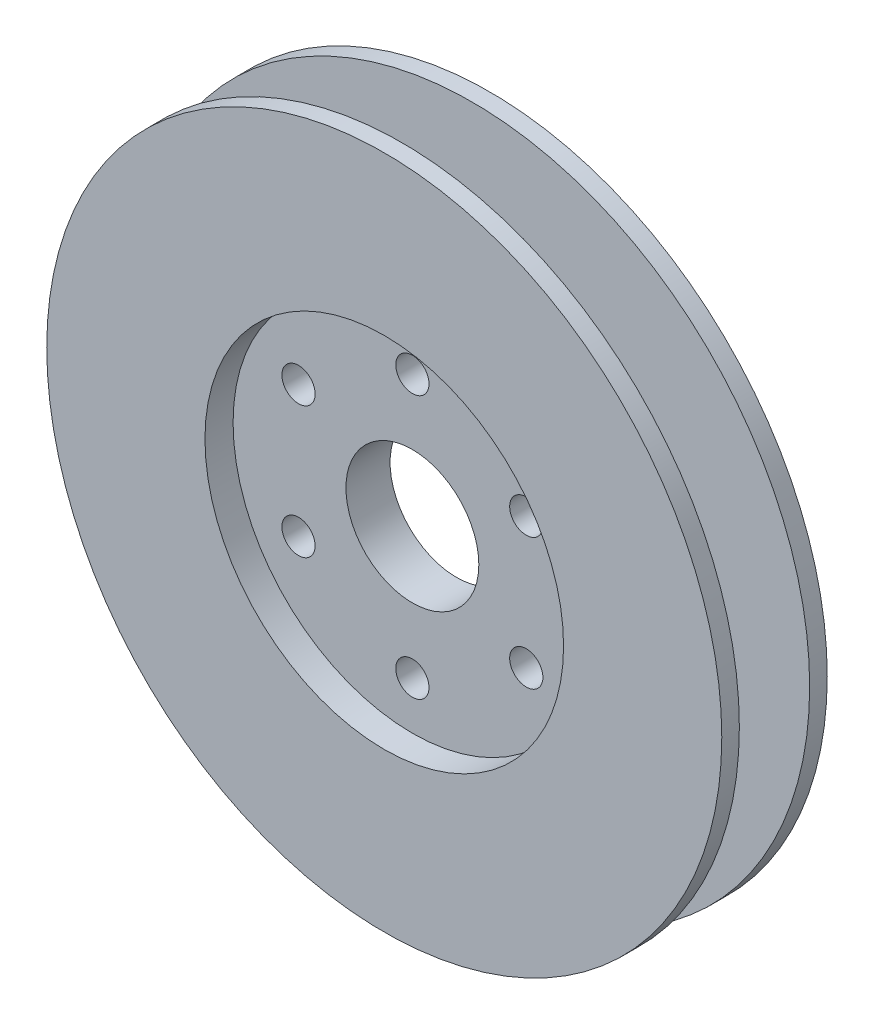
SolidWorks part; units mm, degrees
material "PE High Density Film"
ref_plane "Front Plane" through (0, 0, 0) normal (0, 0, 1) x (1, 0, 0)
ref_plane "Top Plane" through (0, 0, 0) normal (0, 1, 0) x (1, 0, 0)
ref_plane "Right Plane" through (0, 0, 0) normal (1, 0, 0) x (0, 0, -1)
sketch "Sketch1" plane through (0, 0, 0) normal (0, 0, 1) x (1, 0, 0)
  line L0 (0, 0) -> (0, 60.96)
  line L1 (-8.9803, 60.2949) -> (0, 51.3147)
  line L2 (0, 51.3147) -> (8.9803, 60.2949)
  line L3 (36.2849, 48.9849) -> (36.2849, 36.2849)
  line L4 (36.2849, 36.2849) -> (48.9849, 36.2849)
  line L5 (60.2949, 8.9803) -> (51.3147, 0)
  line L6 (51.3147, 0) -> (60.2949, -8.9803)
  line L7 (48.9849, -36.2849) -> (36.2849, -36.2849)
  line L8 (36.2849, -36.2849) -> (36.2849, -48.9849)
  line L9 (8.9803, -60.2949) -> (0, -51.3147)
  line L10 (0, -51.3147) -> (-8.9803, -60.2949)
  line L11 (-36.2849, -48.9849) -> (-36.2849, -36.2849)
  line L12 (-36.2849, -36.2849) -> (-48.9849, -36.2849)
  line L13 (-60.2949, -8.9803) -> (-51.3147, 0)
  line L14 (-51.3147, 0) -> (-60.2949, 8.9803)
  line L15 (-48.9849, 36.2849) -> (-36.2849, 36.2849)
  line L16 (-36.2849, 36.2849) -> (-36.2849, 48.9849)
  arc A0 (-60.2949, -8.9803) -> (-48.9849, -36.2849) centre (0, 0) ccw
  arc A1 (-48.9849, 36.2849) -> (-60.2949, 8.9803) centre (0, 0) ccw
  arc A2 (-36.2849, -48.9849) -> (-8.9803, -60.2949) centre (0, 0) ccw
  arc A3 (8.9803, -60.2949) -> (36.2849, -48.9849) centre (0, 0) ccw
  arc A4 (48.9849, -36.2849) -> (60.2949, -8.9803) centre (0, 0) ccw
  arc A5 (60.2949, 8.9803) -> (48.9849, 36.2849) centre (0, 0) ccw
  arc A6 (36.2849, 48.9849) -> (8.9803, 60.2949) centre (0, 0) ccw
  arc A7 (-8.9803, 60.2949) -> (-36.2849, 48.9849) centre (0, 0) ccw
  circle A8 centre (0, 0) radius 60.96
  point P30 (0, 0)
  dimension "D1" = 121.92
  dimension "D2" = 45
  dimension "D3" = 12.7
  dimension "D4" = 8
extrude "Boss-Extrude1" add sketch "Sketch1" along normal blind 19.05 contours L14 A8 L13 | L16 A8 L15 | L0 A8 L1 | L4 A8 L3 | L6 A8 L5 | L8 A8 L7 | L10 A8 L9 | L12 A8 L11 | L2 A8 L0 | L8 A3 L9 L10 A2 L11 L12 A0 L13 L14 A1 L15 L16 A7 L1 L2 A6 L3 L4 A5 L5 L6 A4 L7 region at (-3.0273, 57.5947, 0) region at (3.0273, 57.5947, 0) region at (-40.7256, 40.7256, 0) region at (40.7256, 40.7256, 0) region at (-57.5947, 0, 0) region at (57.5947, 0, 0) region at (-40.7256, -40.7256, 0) region at (40.7256, -40.7256, 0) region at (0, -57.5947, 0)
sketch "Sketch2" plane through (0, 0, 19.05) normal (0, 0, 1) x (1, 0, 0)
  circle A0 centre (0, 0) radius 12
  dimension "D1" = 24
extrude "Cut-Extrude1" cut sketch "Sketch2" against normal through all contours A0 region at (0, 0, 19.05)
sketch "Sketch3" plane through (0, 0, 19.05) normal (0, 0, 1) x (1, 0, 0)
  circle A0 centre (0, 0) radius 32.385
  dimension "D1" = 64.77
extrude "Cut-Extrude2" cut sketch "Sketch3" against normal blind 5.08
sketch "Sketch4" plane through (0, 0, 0) normal (0, 0, -1) x (-1, 0, 0)
  circle A0 centre (0, 0) radius 28.4
  dimension "D1" = 56.8
extrude "Cut-Extrude3" cut sketch "Sketch4" against normal blind 6
sketch "Sketch5" plane through (0, 0, 6) normal (0, 0, -1) x (-1, 0, 0)
  line L0 (0, 0) -> (0, 23.75) construction
  circle A0 centre (0, 0) radius 23.75 construction
  circle A1 centre (0, 23.75) radius 2.6
  circle A2 centre (20.5681, 11.875) radius 2.6
  circle A3 centre (20.5681, -11.875) radius 2.6
  circle A4 centre (0, -23.75) radius 2.6
  circle A5 centre (-20.5681, -11.875) radius 2.6
  circle A6 centre (-20.5681, 11.875) radius 2.6
  point P17 (0, 0)
  dimension "D1" = 47.5
  dimension "D2" = 5.2
  dimension "D3" = 6
hole_wizard "Ø6.0mm Dowel Hole1" positions "Sketch6" profile "Sketch8" hole size "Ø6.0" standard "ANSI Metric" end condition through all
sketch "Sketch6" plane through (0, 0, 6) normal (0, 0, -1) x (-1, 0, 0)
  point P0 (0, 23.75)
  point P3 (20.5681, 11.875)
  point P6 (20.5681, -11.875)
  point P9 (0, -23.75)
  point P13 (-20.5681, 11.875)
  point P16 (-20.5681, -11.875)
sketch "Sketch8" plane through (0, 23.75, 6) normal (1, 0, 0) x (0, 1, 0)
  line L0 (0, 0) -> (0, 13.05)
  line L1 (0, 13.05) -> (3, 13.05)
  line L2 (3, 13.05) -> (3, 0)
  line L5 (3, 0) -> (0, 0)
  line L11 (0, -6.35) -> (0, 107.95) construction
  dimension "Thru Hole Dia." = 6
  dimension "Thru Hole Depth" = 13.05
ref_plane "Plane1" through (0, 0, 9.525) normal (0, 0, 1) x (1, 0, 0)
sketch "Sketch11" plane through (0, 0, 9.525) normal (0, 0, 1) x (1, 0, 0)
  line L0 (0, 0) -> (0, 50.8) construction
  line L1 (0, 38.1) -> (-15.875, 38.1)
  line L2 (-15.875, 38.1) -> (-15.875, 63.5)
  line L3 (-15.875, 63.5) -> (15.875, 63.5)
  line L4 (15.875, 63.5) -> (15.875, 38.1)
  line L5 (15.875, 38.1) -> (0, 38.1)
  line L6 (0, 50.8) -> (-15.875, 50.8) construction
  line L7 (0, 0) -> (25.4, 0) construction
  dimension "D1" = 25.4
  dimension "D2" = 90
  dimension "D3" = 31.75
  dimension "D4" = 25.4
  dimension "D5" = 50.8
extrude "Cut-Extrude6" [suppressed] cut sketch "Sketch11" against normal mid plane 11.1125
sketch "Sketch12" plane through (0, 0, 0) normal (1, 0, 0) x (0, 0, -1)
  line L0 (0, 0) -> (-19.05, 0) construction
  line L1 (-9.525, 0) -> (-9.525, 60.96) construction
  line L2 (-19.05, 32.385) -> (-19.05, -32.385) construction
  line L3 (-3.175, 60.96) -> (-15.875, 60.96)
  line L4 (-15.875, 60.96) -> (-15.875, 48.26)
  line L6 (-15.875, 48.26) -> (-15.875, 41.91)
  line L7 (-15.875, 41.91) -> (-3.175, 41.91)
  line L8 (-3.175, 41.91) -> (-3.175, 48.26)
  line L10 (-3.175, 48.26) -> (-3.175, 60.96)
  point P3 (0, 0)
  point P6 (0, 0)
  point P7 (0, 0)
  dimension "D1" = 60.96
  dimension "D2" = 12.7
  dimension "D3" = 12.7
  dimension "D4" = 6.35
revolve "Cut-Revolve1" cut sketch "Sketch12" angle 360 about L0
